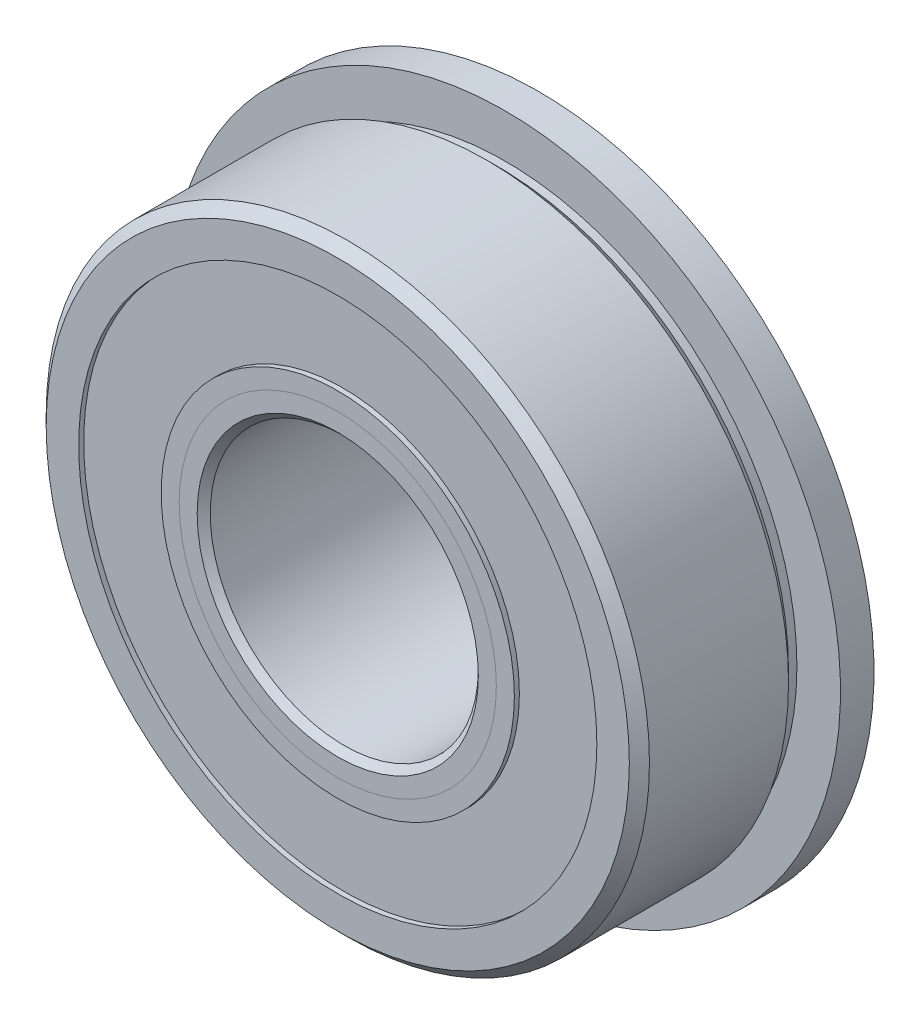
SolidWorks part; units mm, degrees
ref_plane "Front Plane" through (0, 0, 0) normal (0, 0, 1) x (1, 0, 0)
ref_plane "Top Plane" through (0, 0, 0) normal (0, 1, 0) x (1, 0, 0)
ref_plane "Right Plane" through (0, 0, 0) normal (1, 0, 0) x (0, 0, -1)
sketch "Sketch1" plane through (0, 0, 0) normal (1, 0, 0) x (0, 0, -1)
  line L0 (-4.7625, 0) -> (4.7625, 0) construction
  line L1 (0, 14.2875) -> (0, -14.2875) construction
  line L2 (4.2862, 14.2875) -> (-4.2863, 14.2875) construction
  line L3 (-4.2863, 14.2875) -> (-4.7625, 13.8113) construction
  line L4 (-4.7625, 13.8113) -> (-4.7625, 12.2726) construction
  line L5 (-4.7625, 12.2726) -> (-2.7214, 12.2726) construction
  line L6 (4.7625, 12.2726) -> (2.7214, 12.2726) construction
  line L7 (4.7625, 13.8113) -> (4.7625, 12.2726) construction
  line L8 (4.2862, 14.2875) -> (4.7625, 13.8113) construction
  line L9 (0, 14.2875) -> (0, 10.3187) construction
  line L10 (0, 10.3187) -> (0, 6.35) construction
  line L11 (4.7625, 0) -> (6.35, 0) construction
  line L12 (6.35, 8.7376) -> (6.35, -8.7376) construction
  line L13 (6.35, -15.875) -> (6.35, 15.875) construction
  arc A0 (-2.7214, 12.2726) -> (2.7214, 12.2726) centre (0, 10.3187) cw construction
  point P14 (0, 6.35)
  point P20 (6.35, 0)
  point P23 (6.35, 0)
  dimension "OD" = 28.575
  dimension "D1" = 45
  dimension "D2" = 0.4763
  dimension "D3" = 5.4429
  dimension "D4" = 1.9538
  dimension "Width" = 9.525
  dimension "Total Wd" = 11.1125
  dimension "Shaft Dia" = 12.7
  dimension "Inner Ring OD" = 17.4752
  dimension "Flange OD" = 31.75
sketch "Sketch11" plane through (0, 0, 0) normal (0, 0, 1) x (1, 0, 0)
  circle A0 centre (0, 0) radius 6.35 construction
  dimension "Shaft Dia" = 12.7
sketch "Sketch8" plane through (0, 0, 0) normal (1, 0, 0) x (0, 0, -1)
  line L0 (4.2862, 14.2875) -> (-4.2863, 14.2875) construction
  line L1 (4.2862, 14.2875) -> (4.7625, 13.8113) construction
  line L2 (4.7625, 13.8113) -> (4.7625, 12.2726) construction
  line L3 (4.7625, 12.2726) -> (2.7214, 12.2726) construction
  line L4 (-4.7625, 12.2726) -> (-2.7214, 12.2726) construction
  line L5 (-4.7625, 13.8113) -> (-4.7625, 12.2726) construction
  line L6 (-4.2863, 14.2875) -> (-4.7625, 13.8113) construction
  line L7 (4.2862, 14.2875) -> (-4.2863, 14.2875)
  line L8 (4.2862, 14.2875) -> (4.7625, 13.8113)
  line L9 (4.7625, 13.8113) -> (4.7625, 12.2726)
  line L10 (4.7625, 12.2726) -> (2.7214, 12.2726)
  line L11 (-4.7625, 12.2726) -> (-2.7214, 12.2726)
  line L12 (-4.7625, 13.8113) -> (-4.7625, 12.2726)
  line L13 (-4.2863, 14.2875) -> (-4.7625, 13.8113)
  arc A0 (2.7214, 12.2726) -> (-2.7214, 12.2726) centre (0, 10.3187) ccw construction
  arc A1 (2.7214, 12.2726) -> (-2.7214, 12.2726) centre (0, 10.3187) ccw
revolve "Revolve7" add sketch "Sketch8" angle 360 about L0 region at (0, 13.9805, -4.4555)
sketch "Sketch2" plane through (0, 0, 0) normal (1, 0, 0) x (0, 0, -1)
  line L0 (-4.7625, 8.3649) -> (-2.7214, 8.3649)
  line L2 (-4.7625, 8.3649) -> (-4.7625, 7.5121)
  line L3 (-4.7625, 7.5121) -> (-3.9097, 6.6593)
  line L4 (-3.9097, 6.6593) -> (0, 6.6593)
  line L5 (0, 14.2875) -> (0, -14.2875) construction
  line L6 (0, 6.6593) -> (0, 6.9686)
  line L7 (0, 6.9686) -> (0, 6.35) construction
  line L8 (-4.7625, 8.3649) -> (-4.7625, 6.6593) construction
  line L9 (-4.7625, 6.6593) -> (-3.9097, 6.6593) construction
  line L10 (-4.7625, 13.8113) -> (-4.7625, -13.8113) construction
  arc A0 (-2.7214, 8.3649) -> (0, 6.9686) centre (0, 10.3187) ccw
  arc A1 (2.7214, 12.2726) -> (-2.7214, 12.2726) centre (0, 10.3187) ccw construction
  circle A2 centre (0, 10.3187) radius 3.3502 construction
  dimension "D1" = 45
revolve "Revolve2" add sketch "Sketch2" angle 360 about L0
sketch "Sketch3" plane through (0, 0, 0) normal (1, 0, 0) x (0, 0, -1)
  line L0 (-4.7625, 7.5121) -> (-3.9097, 6.6593)
  line L1 (-3.9097, 6.6593) -> (0, 6.6593)
  line L2 (0, 6.6593) -> (0, 6.9686)
  line L3 (-4.7625, 7.5121) -> (-4.7625, 6.6593)
  line L4 (-4.7625, 8.3649) -> (-4.7625, 6.6593) construction
  line L5 (-4.7625, 6.6593) -> (-4.4532, 6.35)
  line L6 (-4.4532, 6.35) -> (5.8738, 6.35)
  line L7 (10.4392, 0) -> (-10.4392, 0) construction
  line L8 (5.8738, 6.35) -> (6.35, 6.8262)
  line L10 (6.35, 6.8262) -> (6.35, 8.7376)
  line L11 (6.35, 8.7376) -> (2.9536, 8.7376)
  line L13 (4.2862, 14.2875) -> (4.7625, 13.8113) construction
  circle A0 centre (0, 10.3187) radius 3.3502 construction
  arc A1 (2.9536, 8.7376) -> (0, 6.9686) centre (0, 10.3187) cw
  point P18 (0, 0)
  dimension "Inner Ring OD" = 17.4752
revolve "Revolve3" add sketch "Sketch3" angle 360 about L0
sketch "Sketch5" plane through (0, 0, 0) normal (1, 0, 0) x (0, 0, -1)
  line L0 (4.7625, 13.8113) -> (4.7625, 12.2726) construction
  line L1 (4.7625, 13.0419) -> (3.175, 13.0419)
  line L2 (4.7625, 13.0419) -> (4.7625, 15.875)
  line L3 (4.7625, 15.875) -> (3.175, 15.875)
  line L4 (3.175, 13.0419) -> (3.175, 15.875)
  line L5 (6.35, 0) -> (-4.7625, 0) construction
  dimension "Flange OD" = 31.75
  dimension "D1" = 1.5875
revolve "Revolve5" add sketch "Sketch5" angle 360 about L5
sketch "Sketch6" plane through (0, 0, 0) normal (1, 0, 0) x (0, 0, -1)
  line L0 (2.3019, 14.2875) -> (2.7781, 13.8113)
  line L1 (4.2862, 14.2875) -> (-4.2863, 14.2875) construction
  line L2 (2.7781, 13.8113) -> (3.175, 13.8113)
  line L3 (3.175, 13.8113) -> (3.175, 14.2875)
  line L4 (3.175, 14.2875) -> (2.3019, 14.2875)
  line L5 (4.2862, 14.2875) -> (4.7625, 13.8113) construction
  line L6 (3.175, 13.0419) -> (3.175, 15.875) construction
  dimension "D1" = 0.3969
revolve "Cut-Revolve1" cut sketch "Sketch6" angle 360 about L0
sketch "Sketch4" plane through (0, 0, 0) normal (1, 0, 0) x (0, 0, -1)
  line L0 (-3.3502, 10.3187) -> (3.3502, 10.3187)
  circle A1 centre (0, 10.3187) radius 3.3502 construction
  arc A2 (-3.3502, 10.3187) -> (3.3502, 10.3187) centre (0, 10.3187) cw
  arc A3 (2.7214, 12.2726) -> (-2.7214, 12.2726) centre (0, 10.3187) ccw construction
revolve "Revolve4" add sketch "Sketch4" angle 360 about L0
ref_axis "Axis1" through (0, 0, -4.7625) along (0, 0, 1)
pattern_circular "CirPattern1" count 12 over 360 about axis through (0, 0, 4.7625) along (0, 0, -1) of bodies 104
sketch "Sketch7" plane through (0, 0, 0) normal (1, 0, 0) x (0, 0, -1)
  line L0 (-4.7625, 12.2726) -> (-2.7214, 12.2726) construction
  line L1 (-4.5244, 12.2726) -> (-3.3502, 12.2726)
  line L2 (-4.5244, 12.2726) -> (-4.5244, 8.3649)
  line L3 (-4.5244, 8.3649) -> (-3.3502, 8.3649)
  line L4 (-3.3502, 12.2726) -> (-3.3502, 8.3649)
  line L5 (-4.7625, 8.3649) -> (-2.7214, 8.3649) construction
  line L6 (-4.2863, 14.2875) -> (-4.7625, 13.8113) construction
  line L7 (4.7625, 12.2726) -> (2.7214, 12.2726) construction
  line L8 (4.5244, 12.2726) -> (3.3502, 12.2726)
  line L9 (4.5244, 12.2726) -> (4.5244, 8.7376)
  line L10 (4.5244, 8.7376) -> (3.3502, 8.7376)
  line L11 (3.3502, 12.2726) -> (3.3502, 8.7376)
  line L12 (6.35, 8.7376) -> (2.9536, 8.7376) construction
  line L13 (4.2862, 14.2875) -> (4.7625, 13.8113) construction
  circle A0 centre (0, 10.3187) radius 3.3502 construction
  point P10 (-4.5244, 14.0494)
  point P21 (4.5244, 14.0494)
revolve "Revolve6" add sketch "Sketch7" angle 360 about L0
sketch "Sketch9" plane through (0, 0, -6.35) normal (0, 0, -1) x (-1, 0, 0)
  line L0 (0, 8.7376) -> (0, 6.8262) construction
  circle A0 centre (0, 0) radius 6.8262 construction
  circle A1 centre (0, 0) radius 8.7376
  circle A2 centre (0, 0) radius 8.7376 construction
  circle A3 centre (0, 0) radius 6.8262 construction
  circle A4 centre (0, 0) radius 7.7819 construction
  circle A5 centre (0, 0) radius 7.9567
  circle A6 centre (0, 0) radius 7.6072
  point P8 (0, 7.7819)
  dimension "D2" = 0.1748
  dimension "D3" = 0.1748
extrude "Cut-Extrude1" cut sketch "Sketch9" against normal blind 0.127
sketch "Sketch10" plane through (0, 0, -4.5244) normal (0, 0, -1) x (-1, 0, 0)
  circle A0 centre (0, 0) radius 8.7376 construction
  circle A1 centre (0, 0) radius 8.7376
  circle A2 centre (0, 0) radius 9.4366
  dimension "D1" = 0.699
extrude "Cut-Extrude2" cut sketch "Sketch10" against normal blind 0.254
equation "\"D2@Sketch1\" = \"Width@Sketch1\"*.05"
equation "\"D3@Sketch1\"=\"Width@Sketch1\"/1.75"
equation "\"D4@Sketch1\"=(((\"OD@Sketch1\"-\"Width@Sketch1\")/2)/3.25)/1.5"
equation "\"Inner Ring OD@Sketch3\"=\"Inner Ring OD@Sketch1\""
equation "\"Flange OD@Sketch5\"=\"Flange OD@Sketch1\""
equation "\"D1@Sketch10\"=\"Inner Ring OD@Sketch1\"*.04"
equation "\"D2@Sketch9\"=\"Inner Ring OD@Sketch1\"*.01"
equation "\"D3@Sketch9\"=\"Inner Ring OD@Sketch1\"*.01"
equation "\"Shaft Dia@Sketch1\"=\"Shaft Dia@Sketch11\""
